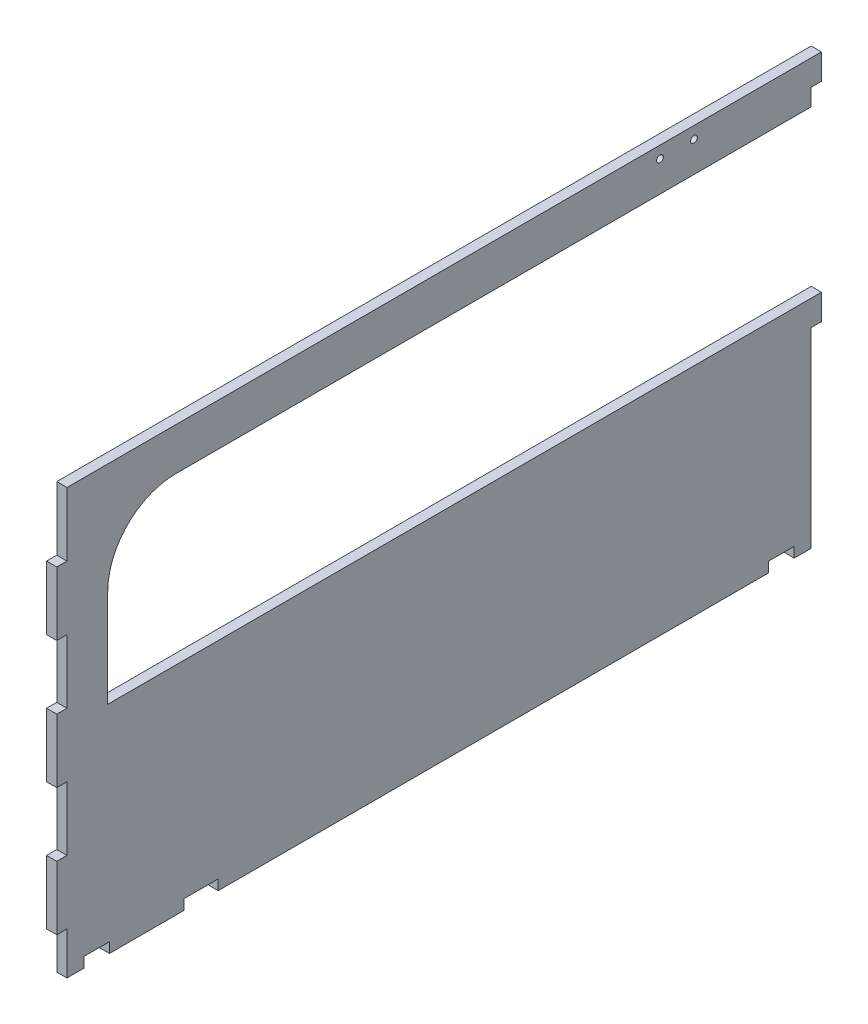
SolidWorks part; units mm, degrees
ref_plane "Front" through (0, 0, 0) normal (0, 0, 1) x (1, 0, 0)
ref_plane "Top" through (0, 0, 0) normal (0, 1, 0) x (1, 0, 0)
ref_plane "Right" through (0, 0, 0) normal (1, 0, 0) x (0, 0, -1)
sketch "Sketch1" plane through (0, 0, 0) normal (1, 0, 0) x (0, 0, -1)
  line L0 (450, 225) -> (450, 250)
  line L1 (0, 0) -> (450, 0)
  line L2 (0, 0) -> (0, 250)
  line L3 (0, 250) -> (450, 250)
  line L4 (450, 0) -> (450, 127.5)
  line L5 (450, 225) -> (30, 225)
  line L7 (450, 127.5) -> (30, 127.5)
  line L8 (30, 225) -> (30, 127.5)
  dimension "D1" = 420
  dimension "D2" = 250
  dimension "D3" = 127.5
  dimension "D4" = 25
  dimension "D5" = 30
extrude "Boss-Extrude1" add sketch "Sketch1" along normal blind 6
sketch "Sketch2" plane through (6, 0, 0) normal (1, 0, 0) x (0, 0, -1)
  line L1 (0, 250) -> (6, 250)
  line L2 (0, 250) -> (0, 212.5)
  line L3 (0, 212.5) -> (6, 212.5)
  line L4 (6, 250) -> (6, 212.5)
  dimension "D1" = 6
  dimension "D2" = 37.5
extrude "Cut-Extrude1" cut sketch "Sketch2" against normal blind 6
pattern_linear "LPattern1" count 4 spacing 75 along (0, -1, 0) of "Cut-Extrude1"
fillet "Fillet1" radius 40 1 edges at (3, 225, -30)
sketch "Sketch3" plane through (0, 0, 0) normal (-1, 0, 0) x (0, 0, 1)
  line L0 (-450, 0) -> (-450, 127.5) construction
  line L1 (-450, 235) -> (-444, 235)
  line L2 (-450, 235) -> (-450, 225)
  line L3 (-450, 225) -> (-444, 225)
  line L4 (-444, 235) -> (-444, 225)
  line L5 (-70, 225) -> (-450, 225) construction
  line L7 (-450, 112.5) -> (-444, 112.5)
  line L8 (-450, 112.5) -> (-450, 0)
  line L9 (-450, 0) -> (-444, 0)
  line L10 (-444, 112.5) -> (-444, 0)
  line L12 (-450, 225) -> (-450, 250) construction
  line L13 (-450, 127.5) -> (-30, 127.5) construction
  line L14 (-6, 0) -> (-450, 0) construction
  dimension "D1" = 6
  dimension "D2" = 10
  dimension "D4" = 15
extrude "Cut-Extrude2" cut sketch "Sketch3" against normal through all
sketch "Sketch4" plane through (0, 0, 0) normal (-1, 0, 0) x (0, 0, 1)
  line L0 (-6, 0) -> (-444, 0) construction
  line L1 (-16, 0) -> (-31, 0)
  line L2 (-16, 0) -> (-16, 6)
  line L3 (-16, 6) -> (-31, 6)
  line L4 (-31, 0) -> (-31, 6)
  line L5 (-6, 62.5) -> (-6, 100) construction
  line L6 (-6, 0) -> (-444, 0) construction
  line L7 (-434, 0) -> (-419, 0)
  line L8 (-434, 0) -> (-434, 6)
  line L9 (-434, 6) -> (-419, 6)
  line L10 (-419, 0) -> (-419, 6)
  line L11 (-444, 0) -> (-444, 112.5) construction
  dimension "D1" = 10
  dimension "D2" = 15
  dimension "D3" = 6
  dimension "D4" = 10
extrude "Cut-Extrude3" cut sketch "Sketch4" against normal through all
sketch "Sketch5" plane through (0, 0, 0) normal (-1, 0, 0) x (0, 0, 1)
  line L0 (-450, 235) -> (-450, 250) construction
  line L1 (-450, 250) -> (-6, 250) construction
  circle A0 centre (-375, 243) radius 2
  circle A1 centre (-355, 243) radius 2
  dimension "D3" = 4
  dimension "D1" = 75
  dimension "D2" = 7
  dimension "D4" = 20
extrude "Cut-Extrude4" cut sketch "Sketch5" against normal through all
sketch "Sketch6" plane through (0, 0, 0) normal (-1, 0, 0) x (0, 0, 1)
  line L0 (-31, 0) -> (-419, 0) construction
  line L1 (-75, 0) -> (-95, 0)
  line L2 (-75, 0) -> (-75, 6)
  line L3 (-75, 6) -> (-95, 6)
  line L4 (-95, 0) -> (-95, 6)
  line L6 (-16, 6) -> (-31, 6) construction
  line L7 (0, 62.5) -> (0, 25) construction
  dimension "D1" = 20
  dimension "D2" = 75
extrude "Cut-Extrude5" cut sketch "Sketch6" against normal through all
